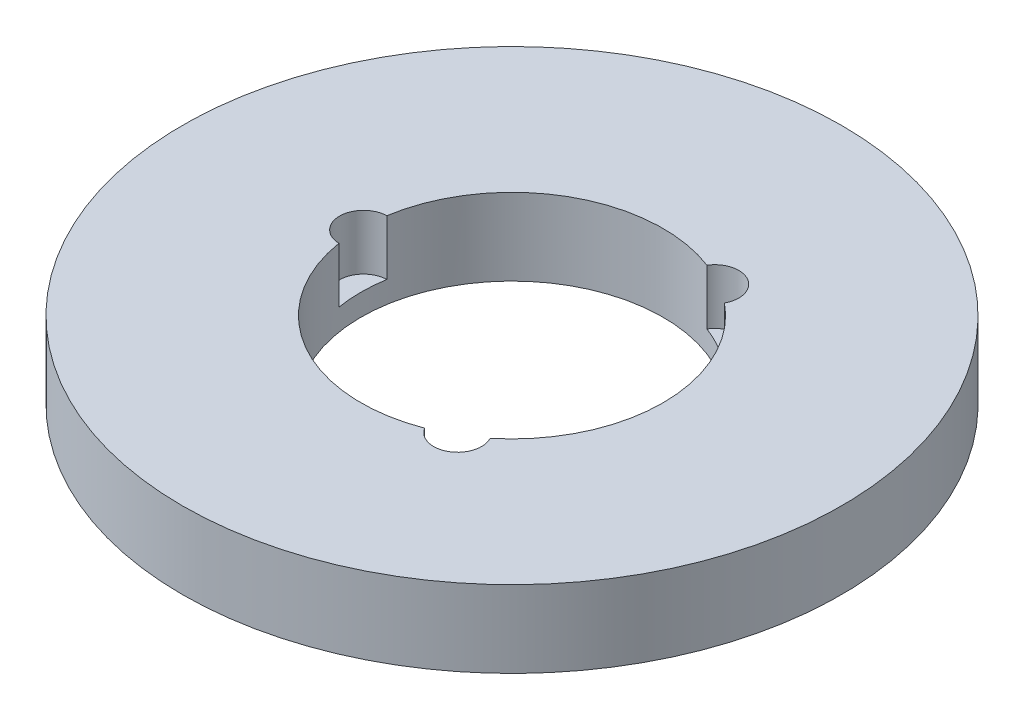
SolidWorks part; units mm, degrees
ref_plane "Front Plane" through (0, 0, 0) normal (0, 0, 1) x (1, 0, 0)
ref_plane "Top Plane" through (0, 0, 0) normal (0, 1, 0) x (1, 0, 0)
ref_plane "Right Plane" through (0, 0, 0) normal (1, 0, 0) x (0, 0, -1)
sketch "Sketch1" plane through (0, 0, 0) normal (0, 1, 0) x (1, 0, 0)
  circle A0 centre (0, 0) radius 60
  dimension "FLANGE_OD" = 120
extrude "Boss-Extrude1" add sketch "Sketch1" along normal blind 14
sketch "Sketch2" plane through (0, 0, 0) normal (0, 1, 0) x (1, 0, 0)
  circle A0 centre (0, 0) radius 27.5
  dimension "BORE_D" = 55
extrude "Cut-Extrude1" cut sketch "Sketch2" along normal through all
sketch "Sketch3" plane through (0, 14, 0) normal (0, 1, 0) x (1, 0, 0)
  circle A0 centre (0, 0) radius 27.0343 construction
  circle A1 centre (-27.0343, 0) radius 4.3631
  dimension "BOLT_D" = 8.7262
  dimension "BOLT_PCD" = 54.0686
extrude "Cut-Extrude2" cut sketch "Sketch3" against normal blind 10.0564
pattern_circular "CirPattern1" count 3 over 360 about axis through (0, 0, 0) along (0, 1, 0) of "Cut-Extrude2"
